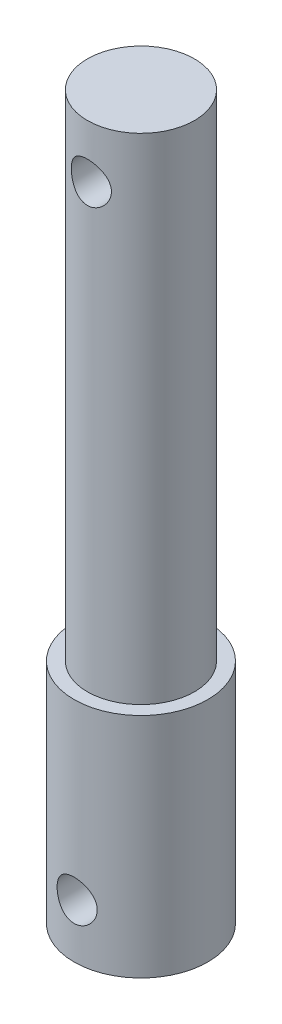
SolidWorks part; units mm, degrees
ref_plane "Front Plane" through (0, 0, 0) normal (0, 0, 1) x (1, 0, 0)
ref_plane "Top Plane" through (0, 0, 0) normal (0, 1, 0) x (1, 0, 0)
ref_plane "Right Plane" through (0, 0, 0) normal (1, 0, 0) x (0, 0, -1)
sketch "Sketch1" plane through (0, 0, 0) normal (0, 1, 0) x (1, 0, 0)
  circle A0 centre (0, 0) radius 5
  circle A1 centre (0, 0) radius 4
  dimension "D1" = 10
  dimension "D2" = 8
extrude "Boss-Extrude1" add sketch "Sketch1" along normal blind 17 contours A1 | A0 A1 region at (-4.8586, 0, 0) region at (0, 0, 0)
extrude "Boss-Extrude2" add sketch "Sketch1<3>" along normal blind 54 contours A1 region at (0, 0, 0)
sketch "Sketch1<3>" plane through (0, 0, 0) normal (0, 1, 0) x (1, 0, 0) same geometry as "Sketch1"
sketch "Sketch2" plane through (0, 0, 0) normal (0, 0, 1) x (1, 0, 0)
  line L0 (4, 54) -> (-4, 54) construction
  circle A0 centre (0, 50) radius 1.5
  circle A1 centre (0, 4) radius 1.5
  dimension "D1" = 4
extrude "Cut-Extrude1" cut sketch "Sketch2" against normal through all both and the other way through all
